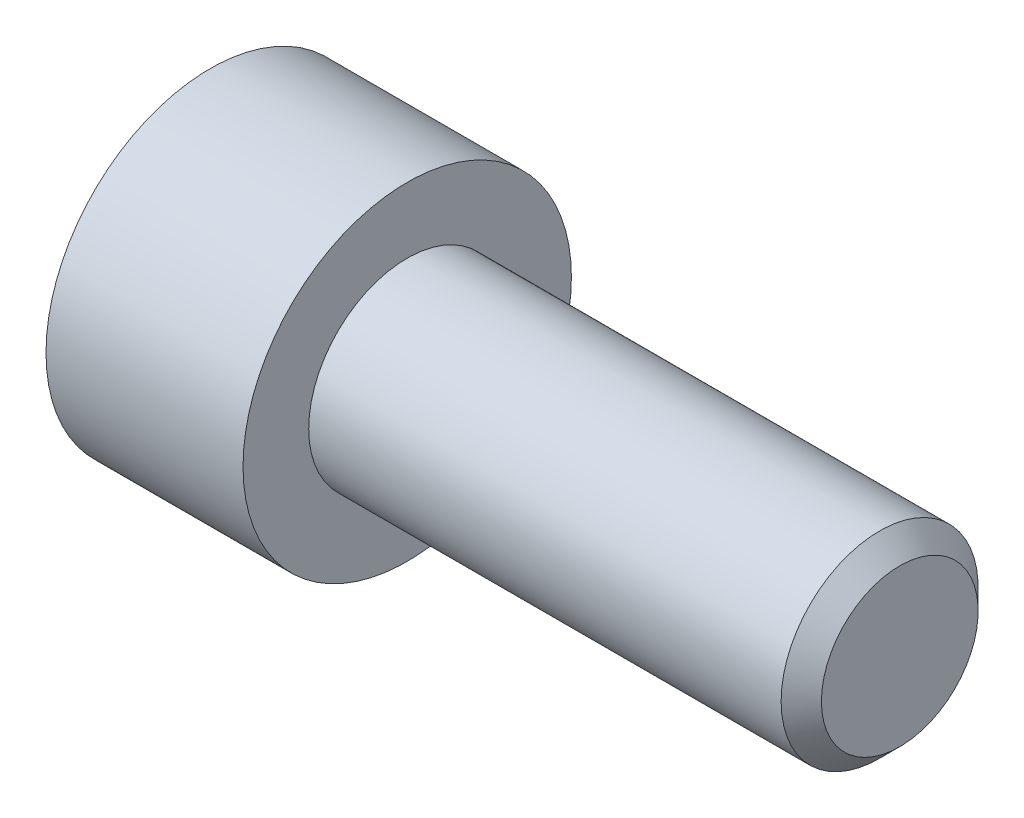
SolidWorks part; units mm, degrees
ref_plane "前视基准面" through (0, 0, 0) normal (0, 0, 1) x (1, 0, 0)
ref_plane "上视基准面" through (0, 0, 0) normal (0, 1, 0) x (1, 0, 0)
ref_plane "右视基准面" through (0, 0, 0) normal (1, 0, 0) x (0, 0, -1)
sketch "草图1" plane through (0, 0, 0) normal (0, 0, 1) x (1, 0, 0)
  line L0 (-6, 0) -> (-6, 5)
  line L1 (-6, 5) -> (0, 5)
  line L2 (0, 5) -> (0, 3)
  line L3 (0, 3) -> (14.3865, 3)
  line L4 (14.3865, 3) -> (15, 2.3865)
  line L5 (15, 2.3865) -> (15, 0)
  line L6 (15, 0) -> (-6, 0)
  line L7 (15, 0) -> (-6, 0) construction
revolve "旋转1" add sketch "草图1" angle 360 about L7 reverse direction yes
cosmetic thread "装饰螺纹线1" parameters "D1"=14, "D2"=4.773
sketch "草图2" plane through (0, 0, 0) normal (0, 0, 1) x (1, 0, 0)
  line L0 (-6, 0) -> (-6, 2.5)
  line L1 (-6, 2.5) -> (-3, 2.5)
  line L2 (-3, 2.5) -> (-2.3301, 0)
  line L3 (-2.3301, 0) -> (-6, 0)
  line L4 (-2.3301, 0) -> (-6, 0) construction
revolve "切除-旋转1" cut sketch "草图2" angle 360 about L4 reverse direction yes
ref_plane "基准面1" through (-6, 0, 0) normal (1, 0, 0) x (0, 0, -1)
sketch "草图3" plane through (-6, 0, 0) normal (1, 0, 0) x (0, 0, -1)
  line L0 (-2.5, 1.4434) -> (-2.5, -1.4434)
  line L1 (-2.5, -1.4434) -> (0, -2.8868)
  line L2 (0, -2.8868) -> (2.5, -1.4434)
  line L3 (2.5, -1.4434) -> (2.5, 1.4434)
  line L4 (2.5, 1.4434) -> (0, 2.8868)
  line L5 (0, 2.8868) -> (-2.5, 1.4434)
extrude "切除-拉伸1" cut sketch "草图3" along normal blind 3
ref_plane "基准面2" through (15, 0, 0) normal (1, 0, 0) x (0, 0, -1)
ref_plane "screw1 XY" through (0, 0, 0) normal (1, 0, 0) x (0, 0, -1)
ref_plane "screw1 XZ" through (0, 0, 0) normal (0, -1, 0) x (1, 0, 0)
ref_plane "screw1 YZ" through (0, 0, 0) normal (0, 0, -1) x (-1, 0, 0)
ref_axis "screw1 X" through (0, 0, 80.9) along (0, 0, -1)
ref_axis "screw1 Y" through (0, -50, 0) along (0, 1, 0)
ref_axis "screw1 Z" through (80.9, 0, 0) along (-1, 0, 0)
sketch3d "screw1"
  point P0 (0, 0, 0)
ref_plane "bolt_to_nut XY" through (15, 0, 0) normal (1, 0, 0) x (0, 0, -1)
ref_plane "bolt_to_nut XZ" through (0, 0, 0) normal (0, -1, 0) x (1, 0, 0)
ref_plane "bolt_to_nut YZ" through (0, 0, 0) normal (0, 0, -1) x (-1, 0, 0)
ref_axis "bolt_to_nut X" through (15, 0, 80.9) along (0, 0, -1)
ref_axis "bolt_to_nut Y" through (15, -50, 0) along (0, 1, 0)
ref_axis "bolt_to_nut Z" through (80.9, 0, 0) along (-1, 0, 0)
sketch3d "bolt_to_nut"
  point P0 (15, 0, 0)
